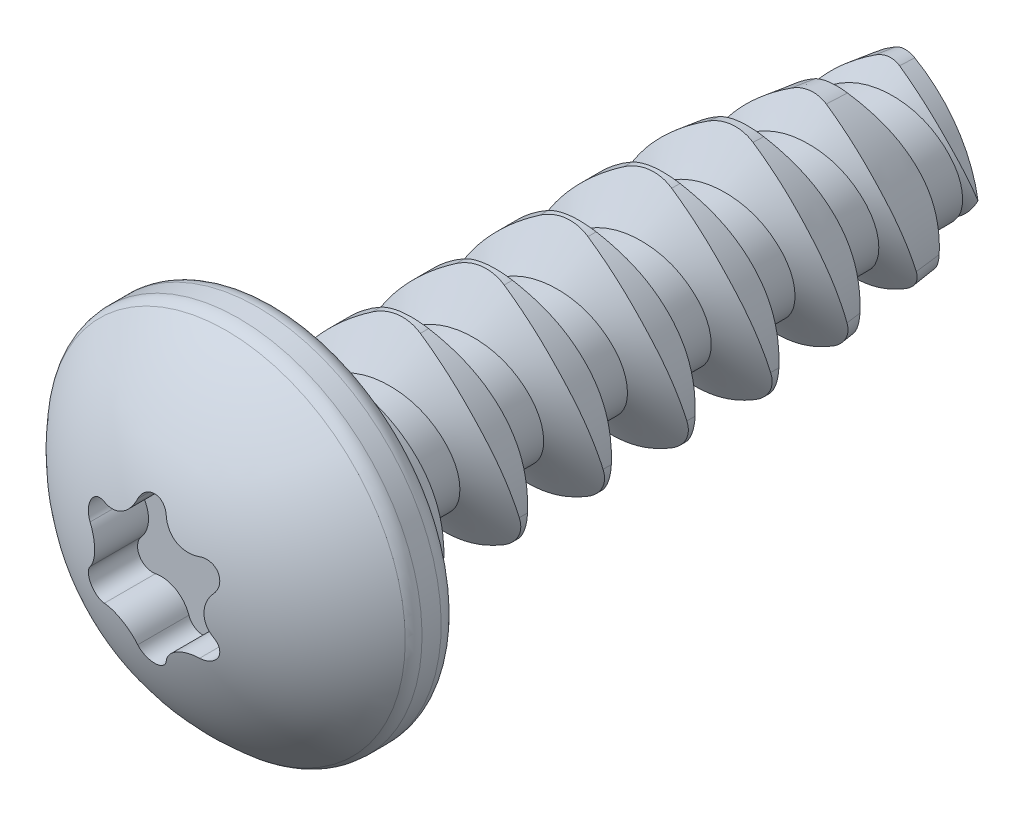
SolidWorks part; units mm, degrees
ref_plane "Front" through (0, 0, 0) normal (0, 0, 1) x (1, 0, 0)
ref_plane "Top" through (0, 0, 0) normal (0, 1, 0) x (1, 0, 0)
ref_plane "Right" through (0, 0, 0) normal (1, 0, 0) x (0, 0, -1)
sketch "Sketch2" plane through (0, 0, 0) normal (1, 0, 0) x (0, 0, -1)
  line L0 (-4.7625, 0) -> (4.7625, 0)
  line L1 (4.7625, 0) -> (4.7625, 1.6129)
  line L2 (4.7625, 1.6129) -> (-4.7625, 1.6129)
  line L3 (-4.7625, 1.6129) -> (-4.7625, 0)
  line L4 (4.7625, 0) -> (6.3754, 0) construction
  line L5 (4.7625, -1.6129) -> (-4.7625, -1.6129) construction
  line L6 (2.827, 1.6129) -> (2.827, 1.4423) construction
  line L7 (4.7625, 1.101) -> (3.7948, 1.2716) construction
  line L8 (3.7948, 1.2716) -> (2.827, 1.4423) construction
  line L9 (2.827, 1.4423) -> (1.8593, 1.6129) construction
  line L10 (1.8593, 1.6129) -> (1.8593, -1.6129) construction
  dimension "D1" = 10
  dimension "Screw OD 'C'" = 3.2258
  dimension "D2" = 3.2258
  dimension "Length" = 9.525
  dimension "Thread Pitch" = 1.9355
revolve "Revolve1" add sketch "Sketch2" angle 360 about L4
sketch "Sketch9" plane through (0, 0, -4.7625) normal (0, 0, -1) x (-1, 0, 0)
  circle A2 centre (0, 0) radius 1.6129
  circle A3 centre (0, 0) radius 1.6129
  dimension "D1" = 0
curve "Helix/Spiral1" pitch 1.27 height 12.7 turns 10 parameters "Pitch"=1.27
sketch "Sketch3" plane through (0, 0, 0) normal (1, 0, 0) x (0, 0, -1)
  line L1 (4.9487, 1.2903) -> (5.7828, 1.2903) construction
  line L4 (4.7625, 1.6129) -> (5.969, 1.6129)
  line L5 (5.969, 1.6129) -> (5.5965, 0.9677)
  line L6 (5.5965, 0.9677) -> (5.135, 0.9677)
  line L7 (5.135, 0.9677) -> (4.7625, 1.6129)
  line L8 (5.3657, 1.6129) -> (5.3657, 0.9677) construction
  dimension "D1" = 1.2065
  dimension "D2" = 0.6452
  dimension "D4" = 60
sweep "Cut-Sweep2" cut profiles "Sketch3" path "Helix/Spiral1"
sketch "Sketch1" plane through (0, 0, 4.7625) normal (0, 0, 1) x (1, 0, 0)
  line L0 (0, 0) -> (-0.8381, -0.4839) construction
  line L1 (0, 0) -> (0.8381, -0.4839) construction
  line L2 (0, 0) -> (0, 0.9677) construction
  line L3 (0, 0) -> (0, -1.3533) construction
  line L4 (0, 0.9677) -> (0, 1.6129) construction
  circle A0 centre (0, 0) radius 1.6129 construction
  arc A1 (0.323, 1.5262) -> (-0.323, 1.5262) centre (0, 0.9677) ccw
  arc A2 (-1.4832, -0.4834) -> (-1.1602, -1.0428) centre (-0.8381, -0.4839) ccw
  arc A3 (1.1602, -1.0428) -> (1.4832, -0.4834) centre (0.8381, -0.4839) ccw
  arc A4 (-1.4832, -0.4834) -> (-0.323, 1.5262) centre (0.8403, -0.4851) cw
  arc A5 (0.323, 1.5262) -> (1.4832, -0.4834) centre (-0.8403, -0.4851) cw
  arc A6 (1.1602, -1.0428) -> (-1.1602, -1.0428) centre (0, 0.9703) cw
  dimension "D1" = 0.6452
  dimension "D2" = 120
  dimension "D5" = 0.0025
  dimension "D3" = 120
extrude "Cut-Extrude2" cut sketch "Sketch1" against normal through all flip side to cut
ref_plane "Plane1" through (0, 0, -1.8593) normal (0, 0, -1) x (-1, 0, 0)
sketch "Sketch6" plane through (0, 0, -1.8593) normal (0, 0, -1) x (-1, 0, 0)
  arc A0 (0.323, 1.5262) -> (-0.323, 1.5262) centre (0, 0.9677) ccw construction
  arc A1 (1.4832, -0.4834) -> (0.323, 1.5262) centre (-0.8403, -0.4851) ccw construction
  arc A2 (1.1602, -1.0428) -> (1.4832, -0.4834) centre (0.8381, -0.4839) ccw construction
  arc A3 (-1.1602, -1.0428) -> (1.1602, -1.0428) centre (0, 0.9703) ccw construction
  arc A4 (-1.4832, -0.4834) -> (-1.1602, -1.0428) centre (-0.8381, -0.4839) ccw construction
  arc A5 (-0.323, 1.5262) -> (-1.4832, -0.4834) centre (0.8403, -0.4851) ccw construction
  arc A6 (0.323, 1.5262) -> (-0.323, 1.5262) centre (0, 0.9677) ccw
  arc A7 (1.4832, -0.4834) -> (0.323, 1.5262) centre (-0.8403, -0.4851) ccw
  arc A8 (1.1602, -1.0428) -> (1.4832, -0.4834) centre (0.8381, -0.4839) ccw
  arc A9 (-1.1602, -1.0428) -> (1.1602, -1.0428) centre (0, 0.9703) ccw
  arc A10 (-1.4832, -0.4834) -> (-1.1602, -1.0428) centre (-0.8381, -0.4839) ccw
  arc A11 (-0.323, 1.5262) -> (-1.4832, -0.4834) centre (0.8403, -0.4851) ccw
extrude "Cut-Extrude4" cut sketch "Sketch6" along normal through all draft 7 flip side to cut draft outward yes
sketch "Sketch7" plane through (0, 0, 0) normal (1, 0, 0) x (0, 0, -1)
  line L0 (-4.7625, 0) -> (-4.7625, 2.491)
  line L1 (-5.0528, 2.7813) -> (-5.3431, 2.7813)
  line L2 (-6.7945, 0) -> (-4.7625, 0)
  line L4 (-6.7945, 0) -> (-7.0848, 0) construction
  arc A0 (-4.7625, 2.491) -> (-5.0528, 2.7813) centre (-5.0528, 2.491) ccw
  arc A1 (-5.3431, 2.7813) -> (-5.5297, 2.7133) centre (-5.3431, 2.491) ccw
  arc A2 (-5.5297, 2.7133) -> (-6.7945, 0) centre (-3.2516, 0) ccw
  point P10 (-5.4462, 2.7813)
  point P11 (-4.7625, 2.7813)
  dimension "D2" = 0.2903
  dimension "D1" = 0.2903
  dimension "Head Height" = 2.032
  dimension "Head Dia" = 5.5626
revolve "Revolve2" add sketch "Sketch7" angle 360 about L4
ref_plane "Plane2" through (0, 0, 6.7945) normal (0, 0, 1) x (1, 0, 0)
sketch "Sketch8" plane through (0, 0, 6.7945) normal (0, 0, 1) x (1, 0, 0)
  line L0 (0, 0) -> (0, 1.1125) construction
  line L1 (0, 0) -> (0.4142, 0.7174) construction
  line L2 (0, 0) -> (-0.4142, 0.7174) construction
  line L3 (-0.4142, 0.7174) -> (0, 0)
  line L4 (0, 0) -> (0.4142, 0.7174)
  arc A0 (-0.4142, 0.7174) -> (-0.2157, 0.9584) centre (-0.6367, 1.1028) ccw
  arc A1 (-0.2157, 0.9584) -> (0.2157, 0.9584) centre (0, 0.8845) cw
  arc A2 (0.2157, 0.9584) -> (0.4142, 0.7174) centre (0.6367, 1.1028) ccw
  circle A3 centre (0, 0) radius 1.1125 construction
  dimension "D1" = 2.225
  dimension "D3" = 0.2281
  dimension "D4" = 0.445
  dimension "D2" = 60
extrude "Cut-Extrude5" cut sketch "Sketch8" against normal blind 0.9144
pattern_circular "CirPattern1" count 6 over 360 about axis through (0, 0, 0) along (0, 0, 1) of "Cut-Extrude5"
sketch "Sketch10" plane through (0, 0, 0) normal (1, 0, 0) x (0, 0, -1)
  line L0 (4.7625, 1.6129) -> (4.7625, -1.6129) construction
  point P0 (1.8593, -1.6129)
  point P1 (-6.7945, 0.9677)
  point P4 (-4.7625, 2.491)
equation "\"D2@Sketch7\"=\"Head Height@Sketch7\"  / 7"
equation "\"D1@Sketch7\"=\"Head Height@Sketch7\"/7"
equation "\"D1@Cut-Extrude5\"=\"Head Height@Sketch7\" * .45"
equation "\"D3@Helix/Spiral1\" = \"Length@Sketch2\" + .125"
equation "\"D1@Sketch3\" = \"Pitch@Helix/Spiral1\"  -   ( \"Pitch@Helix/Spiral1\" * .05 ) "
equation "\"D2@Sketch3\" = \"D2@Sketch2\" * .2"
equation "\"D1@Sketch1\" = \"D2@Sketch2\" * .2"
equation "\"Thread Pitch@Sketch2\" = \"Screw OD 'C'@Sketch2\" * .6"
equation "\"D4@Sketch8\" = \"Head Dia@Sketch7\" * .08"
equation "\"D3@Sketch8\" = \"Head Dia@Sketch7\" * .041"
equation "\"D1@Sketch8\" = \"Head Dia@Sketch7\" * .4"
